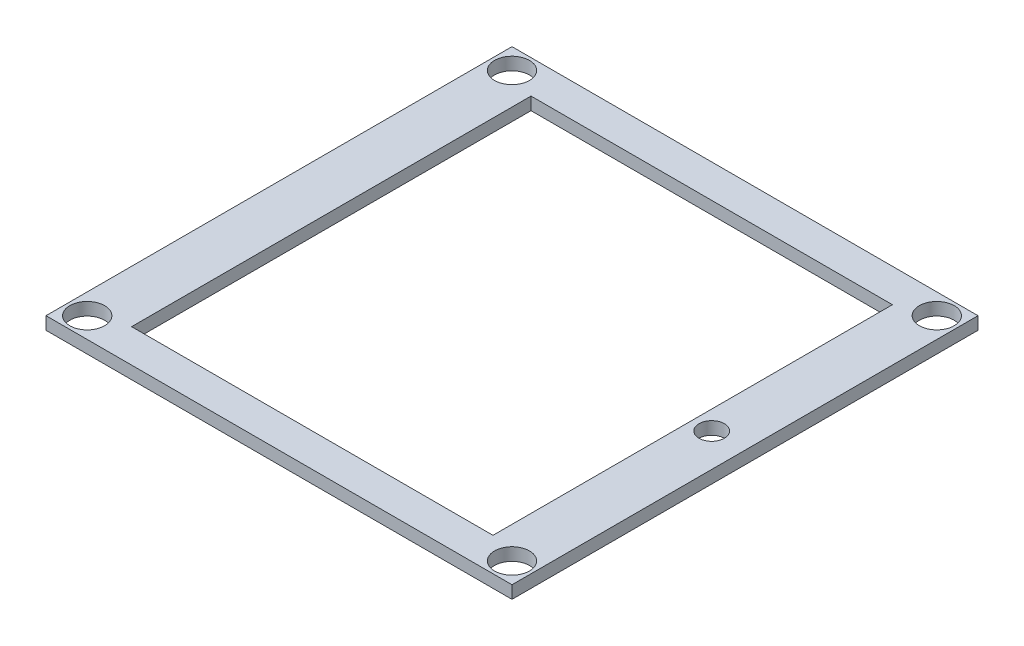
SolidWorks part; units mm, degrees
ref_plane "Front Plane" through (0, 0, 0) normal (0, 0, 1) x (1, 0, 0)
ref_plane "Top Plane" through (0, 0, 0) normal (0, 1, 0) x (1, 0, 0)
ref_plane "Right Plane" through (0, 0, 0) normal (1, 0, 0) x (0, 0, -1)
sketch "Sketch1" plane through (0, 0, 0) normal (0, 1, 0) x (1, 0, 0)
  line L0 (147, 147) -> (147, -147)
  line L1 (-147, -147) -> (147, -147)
  line L2 (-147, -147) -> (-147, 147)
  line L3 (-147, 147) -> (147, 147)
  line L5 (-147, -147) -> (147, 147) construction
  line L6 (-147, 147) -> (147, -147) construction
  line L7 (-114, -126) -> (114, -126)
  line L8 (-114, -126) -> (-114, 126)
  line L9 (-114, 126) -> (114, 126)
  line L10 (114, -126) -> (114, 126)
  line L11 (-114, -126) -> (114, 126) construction
  line L12 (-114, 126) -> (114, -126) construction
  point P0 (0, 0)
  point P5 (0, 0)
  dimension "D1" = 294
  dimension "D2" = 228
  dimension "D3" = 252
extrude "Boss-Extrude1" add sketch "Sketch1" along normal blind 8
sketch "Sketch2" plane through (0, 0, 0) normal (0, 1, 0) x (1, 0, 0)
  line L1 (147, 147) -> (-147, 147) construction
  line L2 (147, -147) -> (147, 147) construction
  circle A0 centre (134, 134) radius 11
  dimension "D1" = 22
  dimension "D2" = 13
  dimension "D3" = 13
extrude "Cut-Extrude1" cut sketch "Sketch2" along normal through all
sketch "Sketch4" plane through (0, 8, 0) normal (0, 1, 0) x (1, 0, 0)
  line L0 (134, -864) -> (134, 49136) construction
  circle A0 centre (126, 0) radius 8
  dimension "D1" = 8
  dimension "D2" = 16
mirror "Mirror2" about plane through (0, 0, 0) normal (0, 0, 1) of "Cut-Extrude1"
extrude "Cut-Extrude2" cut sketch "Sketch4" against normal through all
mirror "Mirror3" about plane through (0, 0, 0) normal (1, 0, 0) of "Mirror2", "Cut-Extrude1"
